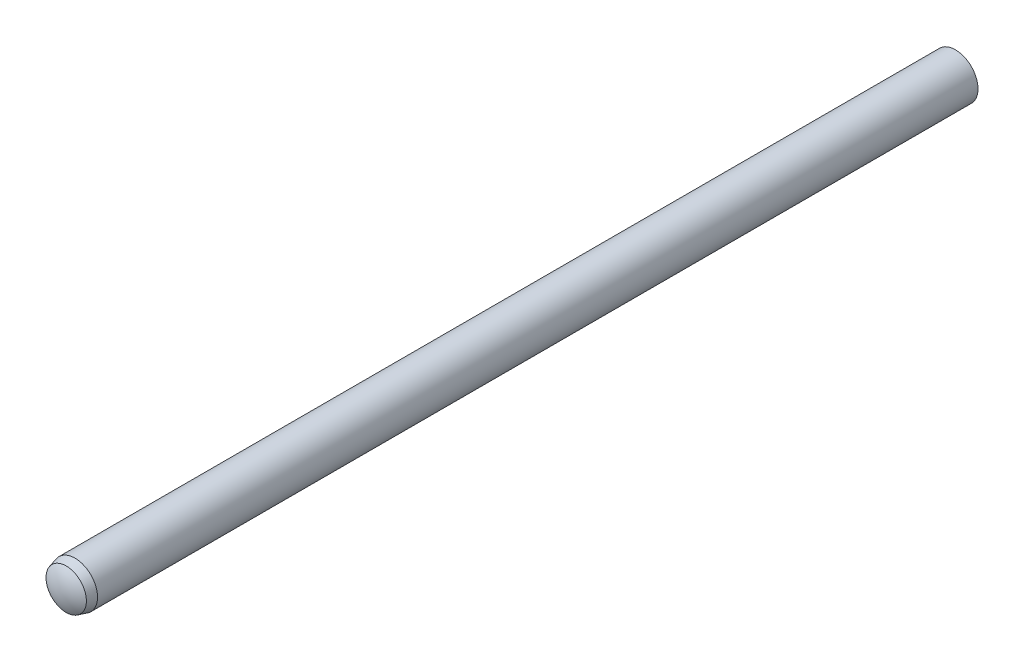
SolidWorks part; units mm, degrees
material "AISI 4130 Steel, annealed at 865C"
ref_plane "Front Plane" through (0, 0, 0) normal (0, 0, 1) x (1, 0, 0)
ref_plane "Top Plane" through (0, 0, 0) normal (0, 1, 0) x (1, 0, 0)
ref_plane "Right Plane" through (0, 0, 0) normal (1, 0, 0) x (0, 0, -1)
sketch "Sketch1" plane through (0, 0, 0) normal (0, 0, 1) x (1, 0, 0)
  circle A0 centre (0, 0) radius 2
  point P3 (0, 2)
  dimension "Diameter" = 4
sketch "Sketch2" plane through (0, 0, 0) normal (1, 0, 0) x (0, 0, -1)
  line L0 (-40, 0) -> (40, 0) construction
  line L1 (-40, 0) -> (-40, 2) construction
  line L2 (-40, 2) -> (40, 2)
  line L3 (40, 2) -> (40, 0) construction
  line L4 (-39.48, 1.791) -> (-38.7, 2)
  arc A0 (-40, 0) -> (-39.48, 1.791) centre (-36.6557, 0) cw
  arc A1 (40, 0) -> (39.4, 2) centre (36.3667, 0) ccw
  point P2 (0, 0)
  point P11 (-36, 0)
  point P13 (36, 0)
  dimension "D1" = 15
  dimension "D2" = 0.6
  dimension "D3" = 1.3
  dimension "D4" = 0.78
  dimension "D5" = 4
  dimension "D6" = 4
sketch "Sketch3" plane through (0, 0, 0) normal (1, 0, 0) x (0, 0, -1)
  line L0 (-40, 0) -> (40, 0) construction
  line L1 (-39.48, 1.791) -> (-38.7, 2) construction
  line L2 (-40, 0) -> (40, 0)
  line L3 (-39.48, 1.791) -> (-38.7, 2)
  line L4 (-38.7, 2) -> (39.4, 2)
  arc A0 (40, 0) -> (39.4, 2) centre (36.3667, 0) ccw construction
  arc A1 (-39.48, 1.791) -> (-40, 0) centre (-36.6557, 0) ccw construction
  arc A2 (40, 0) -> (39.4, 2) centre (36.3667, 0) ccw
  arc A3 (-39.48, 1.791) -> (-40, 0) centre (-36.6557, 0) ccw
revolve "Revolve1" add sketch "Sketch3" angle 360 about L2
ref_axis "Axis1" through (0, 0, -39.4) along (0, 0, 1)
equation "\"D2@Sketch2\" = \"Diameter@Sketch1\" * .15"
equation "\"D3@Sketch2\" = \"Diameter@Sketch1\" * .325"
equation "\"D4@Sketch2\" = \"D3@Sketch2\" * .6"
equation "\"D5@Sketch2\"=\"Diameter@Sketch1\""
equation "\"D6@Sketch2\"=\"D5@sketch2\""
